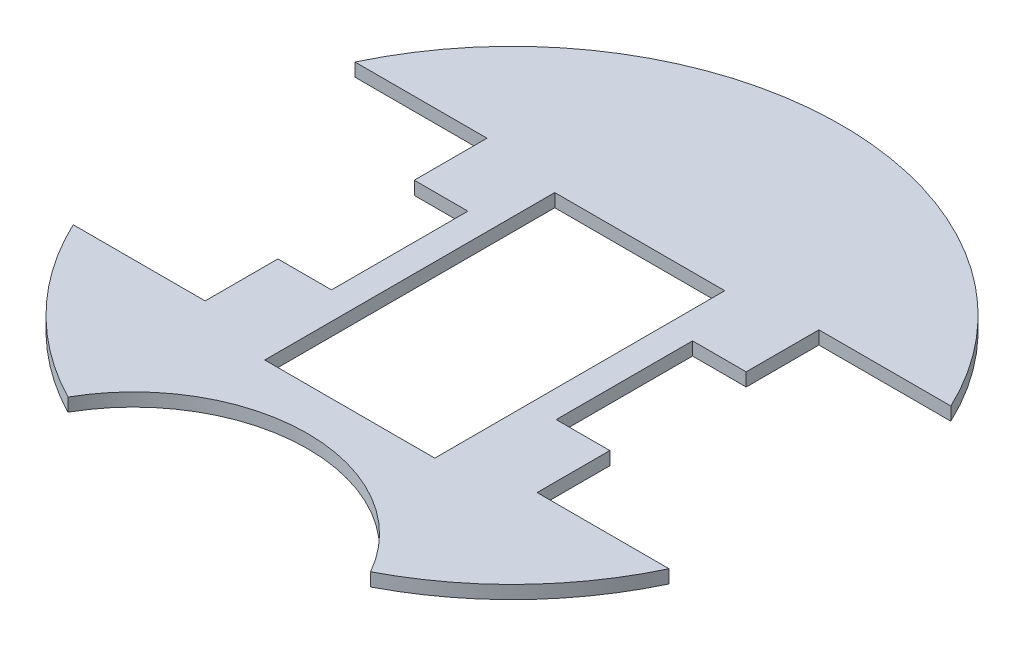
SolidWorks part; units mm, degrees
ref_plane "Front Plane" through (0, 0, 0) normal (0, 0, 1) x (1, 0, 0)
ref_plane "Top Plane" through (0, 0, 0) normal (0, 1, 0) x (1, 0, 0)
ref_plane "Right Plane" through (0, 0, 0) normal (1, 0, 0) x (0, 0, -1)
sketch "Sketch1" plane through (0, 0, 0) normal (0, 1, 0) x (1, 0, 0)
  line L0 (0, -83.2398) -> (-33.2911, -64.4046) construction
  line L1 (0, -83.2398) -> (0, 0) construction
  arc A0 (33.2911, -64.4046) -> (-33.2911, -64.4046) centre (0, 0) ccw
  arc A1 (33.2911, -64.4046) -> (-33.2911, -64.4046) centre (0, -83.2398) ccw
  dimension "D1" = 145
  dimension "D2" = 76.5
  dimension "D3" = 60.5
extrude "Boss-Extrude1" add sketch "Sketch1" along normal blind 2.9
sketch "solenoid placement" plane through (0, 2.9, 0) normal (0, 1, 0) x (1, 0, 0)
  line L4 (-18.7, -35.7) -> (18.7, -35.7)
  line L5 (18.7, -35.7) -> (18.7, 28.1)
  line L6 (18.7, 28.1) -> (-18.7, 28.1)
  line L7 (-18.7, 28.1) -> (-18.7, -35.7)
  line L8 (-18.7, -35.7) -> (18.7, -35.7)
  line L9 (18.7, -35.7) -> (18.7, 28.1)
  line L10 (18.7, 28.1) -> (-18.7, 28.1)
  line L11 (-18.7, 28.1) -> (-18.7, -35.7)
  circle A1 centre (0, 0) radius 72.5 construction
  arc A2 (33.2911, -64.4046) -> (-33.2911, -64.4046) centre (0, 0) ccw construction
  dimension "D1" = 0
extrude "Cut-Extrude1" cut sketch "solenoid placement" against normal through all
sketch "Sketch2" plane through (0, 2.9, 0) normal (0, 1, 0) x (1, 0, 0)
  line L0 (0, 0) -> (0, 72.5) construction
  line L1 (-36.51, -15) -> (-24.71, -15)
  line L2 (36.51, -31) -> (65.5382, -31)
  line L3 (-36.51, 15) -> (-24.71, 15)
  line L4 (-24.71, -15) -> (-24.71, 15)
  line L5 (-36.51, 15) -> (-36.51, 31)
  line L6 (-36.51, 31) -> (-65.5382, 31)
  line L7 (-36.51, -15) -> (-36.51, -31)
  line L8 (-36.51, -31) -> (-65.5382, -31)
  line L9 (36.51, -15) -> (36.51, -31)
  line L10 (36.51, 31) -> (65.5382, 31)
  line L11 (36.51, 15) -> (36.51, 31)
  line L12 (24.71, -15) -> (24.71, 15)
  line L13 (36.51, 15) -> (24.71, 15)
  line L14 (36.51, -15) -> (24.71, -15)
  arc A0 (33.2911, -64.4046) -> (-33.2911, -64.4046) centre (0, 0) ccw construction
  arc A1 (65.5382, 31) -> (65.5382, -31) centre (0, 0) cw
  arc A2 (-65.5382, 31) -> (-65.5382, -31) centre (0, 0) ccw
  dimension "D1" = 62
extrude "Cut-Extrude2" cut sketch "Sketch2" against normal through all
equation "\"smallPulleyTeeth\"= 15"
equation "\"largePulleyTeeth\"= 30"
equation "\"eighthThick\"= 2.9mm"
equation "\"sixteenthThick\" = 1.7mm"
equation "\"quarterThick\"=5.9mm"
equation "\"OD\" = 145mm"
equation "\"puckAngle\" = 60.5deg"
equation "\"D1@Sketch1\"=\"OD\""
equation "\"puckDiam\" = 76.5mm"
equation "\"D2@Sketch1\"=\"puckDiam\""
equation "\"D3@Sketch1\"=\"puckAngle\""
equation "\"D1@Boss-Extrude1\"=\"eighthThick\""
equation "\"axlePress\" = 5.9mm"
equation "\"press\" = 0.2mm"
equation "\"wheelClear\" = 0.3mm"
equation "\"10-32clear\" = 4.5mm"
equation "\"6-32clear\" = 3.3mm"
equation "\"8-32clear\" = 4.0mm"
equation "\"wheelHeight\" = 24mm"
equation "\"wheelWell\" = 62mm"
equation "\"D1@Sketch2\"=\"wheelWell\""
